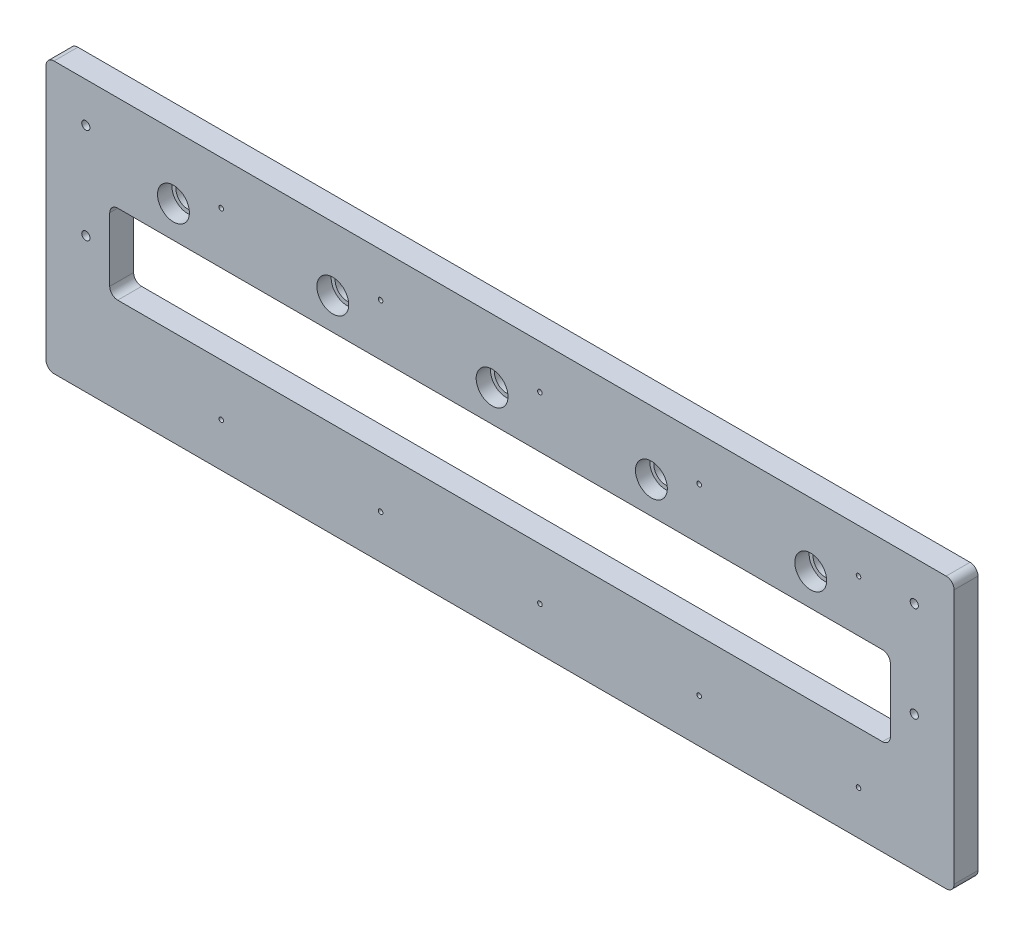
SolidWorks part; units mm, degrees
ref_plane "Front Plane" through (0, 0, 0) normal (0, 0, 1) x (1, 0, 0)
ref_plane "Top Plane" through (0, 0, 0) normal (0, 1, 0) x (1, 0, 0)
ref_plane "Right Plane" through (0, 0, 0) normal (1, 0, 0) x (0, 0, -1)
sketch "Sketch2" plane through (0, 0, 0) normal (0, 0, 1) x (1, 0, 0)
  line L0 (330.2, 107.95) -> (330.2, -107.95)
  line L1 (-393.7, -107.95) -> (330.2, -107.95)
  line L2 (-393.7, -107.95) -> (-393.7, 107.95)
  line L3 (-393.7, 107.95) -> (330.2, 107.95)
  line L5 (-393.7, -107.95) -> (393.7, 107.95) construction
  line L6 (-393.7, 107.95) -> (393.7, -107.95) construction
  point P0 (0, 0)
  dimension "D1" = 787.4
  dimension "D2" = 215.9
extrude "Boss-Extrude1" add sketch "Sketch2" along normal blind 19.05
sketch "Sketch13" plane through (0, 0, 19.05) normal (0, 0, 1) x (1, 0, 0)
  line L1 (-336.55, -31.75) -> (273.05, -31.75)
  line L2 (-342.9, -25.4) -> (-342.9, 25.4)
  line L3 (-336.55, 31.75) -> (273.05, 31.75)
  line L4 (279.4, -25.4) -> (279.4, 25.4)
  line L5 (-342.9, -31.75) -> (279.4, 31.75) construction
  line L6 (-342.9, 31.75) -> (279.4, -31.75) construction
  line L7 (-393.7, 107.95) -> (-393.7, -107.95) construction
  line L9 (330.2, -107.95) -> (330.2, 107.95) construction
  arc A0 (273.05, 31.75) -> (279.4, 25.4) centre (273.05, 25.4) cw
  arc A1 (273.05, -31.75) -> (279.4, -25.4) centre (273.05, -25.4) ccw
  arc A2 (-336.55, -31.75) -> (-342.9, -25.4) centre (-336.55, -25.4) cw
  arc A3 (-342.9, 25.4) -> (-336.55, 31.75) centre (-336.55, 25.4) cw
  point P19 (279.4, 0)
  dimension "D3" = 6.35
  dimension "D1" = 63.5
  dimension "D2" = 50.8
  dimension "D4" = 50.8
extrude "Cut-Extrude3" cut sketch "Sketch13" against normal through all
hole_wizard "#27 (0.144) Diameter Hole1" positions "Sketch14" profile "Sketch15" hole size "#27" standard "ANSI Inch" end condition through all
sketch "Sketch14" plane through (0, 0, 0) normal (0, 0, -1) x (-1, 0, 0)
  line L1 (-254, -73.025) -> (254, -73.025) construction
  line L2 (-254, -73.025) -> (-254, 73.025) construction
  line L3 (-254, 73.025) -> (254, 73.025) construction
  line L4 (254, -73.025) -> (254, 73.025) construction
  line L5 (-254, -73.025) -> (254, 73.025) construction
  line L6 (-254, 73.025) -> (254, -73.025) construction
  point P1 (0, 0)
  point P22 (-254, 73.025)
  point P36 (-127, 73.025)
  point P37 (0, 73.025)
  point P38 (127, 73.025)
  point P39 (254, 73.025)
  point P40 (-127, -73.025)
  point P41 (0, -73.025)
  point P42 (127, -73.025)
  point P43 (254, -73.025)
  point P44 (-254, -73.025)
  dimension "D1" = 146.05
  dimension "D2" = 508
  dimension "D3" = 5
  dimension "D4" = 2
sketch "Sketch15" plane through (0, 0, 0) normal (1, 0, 0) x (0, 1, 0)
  line L0 (0, 0) -> (0, 19.05)
  line L1 (0, 19.05) -> (1.8288, 19.05)
  line L2 (1.8288, 19.05) -> (1.8288, 0)
  line L5 (1.8288, 0) -> (0, 0)
  line L11 (0, -6.35) -> (0, 107.95) construction
  dimension "Thru Hole Dia." = 3.6576
  dimension "Thru Hole Depth" = 19.05
hole_wizard "1/4 Clearance Hole1" positions "Sketch18" profile "Sketch19" hole size "1/4" standard "ANSI Inch" end condition through all
sketch "Sketch18" plane through (0, 0, 0) normal (0, 0, -1) x (-1, 0, 0)
  line L0 (-330.2, -107.95) -> (-330.2, 107.95) construction
  line L1 (-330.2, 107.95) -> (393.7, 107.95) construction
  line L2 (393.7, 107.95) -> (393.7, -107.95) construction
  line L5 (-298.45, 76.2) -> (361.95, 76.2) construction
  line L6 (-298.45, 76.2) -> (-298.45, 0) construction
  line L7 (-298.45, 0) -> (361.95, 0) construction
  line L8 (361.95, 76.2) -> (361.95, 0) construction
  point P0 (-298.45, 76.2)
  point P2 (361.95, 76.2)
  point P73 (361.95, 0)
  point P128 (-298.45, 0)
  dimension "D1" = 31.75
  dimension "D2" = 31.75
  dimension "D3" = 31.75
  dimension "D4" = 31.75
  dimension "D5" = 76.2
sketch "Sketch19" plane through (298.45, 76.2, 0) normal (1, 0, 0) x (0, 1, 0)
  line L0 (0, 0) -> (0, 19.05)
  line L1 (0, 19.05) -> (3.2639, 19.05)
  line L2 (3.2639, 19.05) -> (3.2639, 0)
  line L5 (3.2639, 0) -> (0, 0)
  line L11 (0, -6.35) -> (0, 107.95) construction
  dimension "Thru Hole Dia." = 6.5278
  dimension "Thru Hole Depth" = 19.05
fillet "Fillet1" radius 6.35 4 edges at (330.2, 107.95, 9.525) (330.2, -107.95, 9.525) (-393.7, -107.95, 9.525) (-393.7, 107.95, 9.525)
sketch "Sketch20" plane through (0, 0, 0) normal (0, 0, -1) x (-1, 0, 0)
  line L0 (-330.2, -101.6) -> (-330.2, 101.6) construction
  line L1 (-323.85, 107.95) -> (387.35, 107.95) construction
  circle A0 centre (-215.9, 57.15) radius 9.525
  dimension "D1" = 114.3
  dimension "D2" = 50.8
  dimension "D3" = 19.05
extrude "Cut-Extrude4" cut sketch "Sketch20" against normal through all
sketch "Sketch21" plane through (0, 0, 19.05) normal (0, 0, 1) x (1, 0, 0)
  circle A0 centre (215.9, 57.15) radius 12.7
  dimension "D1" = 25.4
extrude "Cut-Extrude5" cut sketch "Sketch21" against normal blind 11.43
pattern_linear "LPattern1" count 5 spacing 127 along (-1, 0, 0) of "Cut-Extrude4", "Cut-Extrude5"
